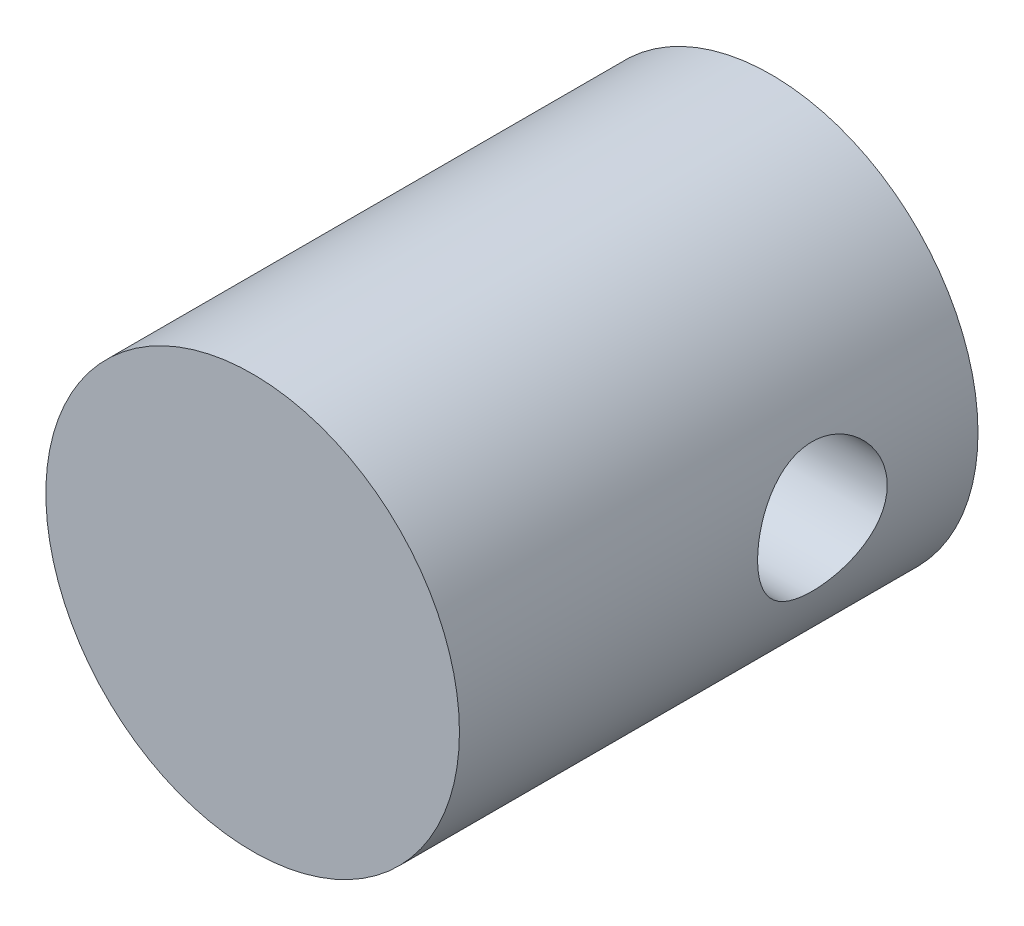
SolidWorks part; units mm, degrees
ref_plane "Front Plane" through (0, 0, 0) normal (1, 0, 0) x (0, 1, 0)
ref_plane "Top Plane" through (0, 0, 0) normal (0, 0, 1) x (0, 1, 0)
ref_plane "Right Plane" through (0, 0, 0) normal (0, 1, 0) x (-1, 0, 0)
sketch "Sketch1" plane through (0, 0, 0) normal (0, 0, 1) x (0, 1, 0)
  circle A0 centre (0, 0) radius 12.6619
  dimension "D1" = 25.3238
extrude "Boss-Extrude1" add sketch "Sketch1" along normal blind 31.75
sketch "Sketch2" plane through (0, 0, 0) normal (1, 0, 0) x (0, 1, 0)
  line L0 (0, 0) -> (0, 9.525) construction
  line L1 (0, 9.525) -> (0, 31.75) construction
  line L2 (12.6619, 31.75) -> (-12.6619, 31.75) construction
  circle A0 centre (0, 9.525) radius 3.9688
  dimension "D1" = 7.9375
  dimension "D2" = 9.525
extrude "Cut-Extrude1" cut sketch "Sketch2" against normal through all both and the other way through all
